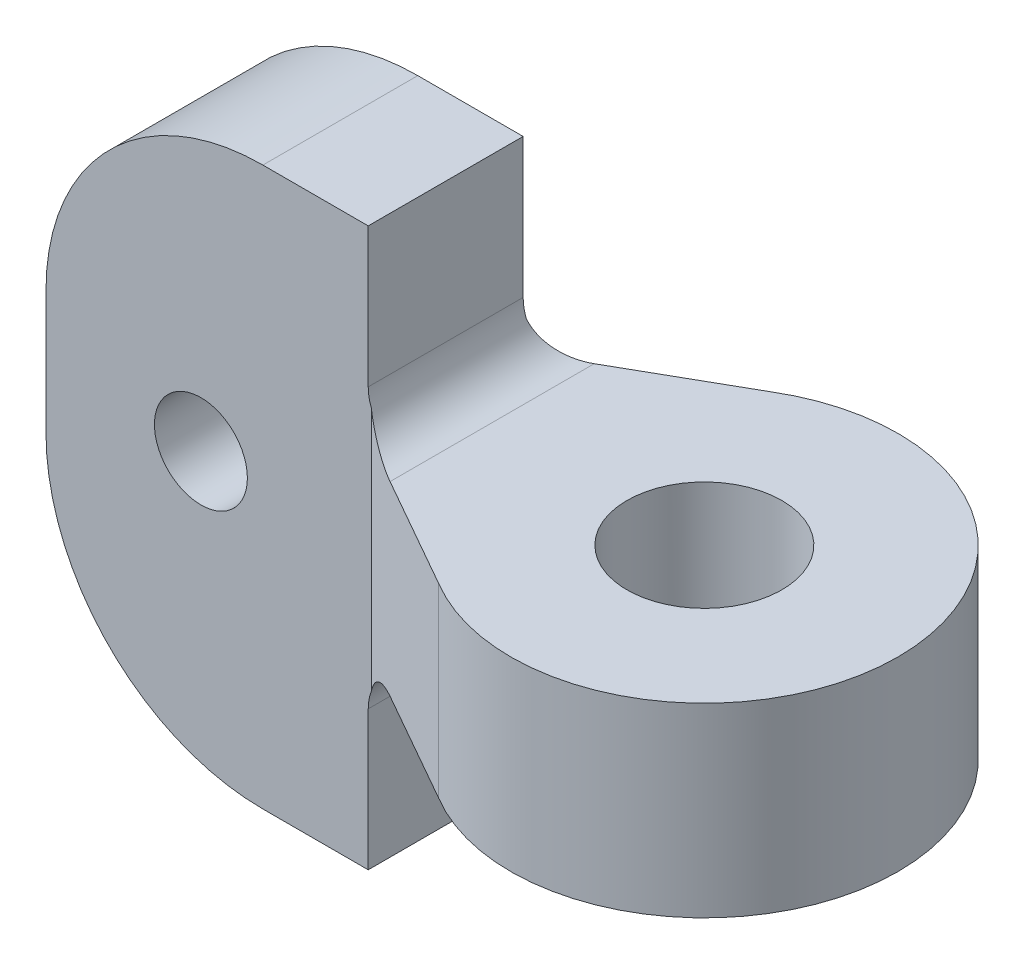
SolidWorks part; units mm, degrees
ref_plane "Alzado" through (0, 0, 0) normal (0, 0, 1) x (1, 0, 0)
ref_plane "Planta" through (0, 0, 0) normal (0, 1, 0) x (1, 0, 0)
ref_plane "Vista lateral" through (0, 0, 0) normal (1, 0, 0) x (0, 0, -1)
sketch "Croquis1" plane through (0, 0, 0) normal (0, 0, 1) x (1, 0, 0)
  line L0 (11.25, 17.1) -> (11.25, 11.1)
  line L1 (5.75, -0.9) -> (11.25, -0.9)
  line L2 (-1.25, 6.1) -> (-1.25, 10.1)
  line L3 (5.75, 17.1) -> (11.25, 17.1)
  line L4 (11.25, 11.1) -> (23.75, 11.1)
  line L5 (-1.25, -0.9) -> (1.25, 0.9) construction
  line L6 (-1.25, 17.1) -> (-1.0254, 14.0276) construction
  line L7 (23.75, 11.1) -> (23.75, 5.1)
  line L9 (23.75, 5.1) -> (11.25, 5.1)
  line L10 (11.25, 5.1) -> (11.25, -0.9)
  line L13 (11.25, 17.1) -> (-1.25, 17.1) construction
  circle A0 centre (3.75, 8.1) radius 1.5
  arc A1 (-1.25, 10.1) -> (5.75, 17.1) centre (5.75, 10.1) cw
  arc A2 (5.75, -0.9) -> (-1.25, 6.1) centre (5.75, 6.1) cw
  point P0 (0, 0)
  dimension "D6" = 3
  dimension "D4" = 7
  dimension "D5" = 7
  dimension "D1" = 25
  dimension "D2" = 18
  dimension "D3" = 12.5
  dimension "D7" = 5
  dimension "D8" = 9
  dimension "D9" = 6
  dimension "D10" = 6
extrude "Saliente-Extruir1" add sketch "Croquis1" along normal blind 15
sketch "Croquis2" plane through (0, 0, 0) normal (0, 1, 0) x (1, 0, 0)
  line L0 (23.75, -7.5) -> (11.25, -7.5) construction
  line L1 (23.75, -15) -> (23.75, 0) construction
  line L2 (11.25, -15) -> (11.25, 0) construction
  line L3 (17.5, -1.25) -> (11.25, 0)
  line L4 (17.5, -13.75) -> (11.25, -15)
  line L5 (11.25, -15) -> (11.25, -17.9613)
  line L6 (11.25, -17.9613) -> (29.6635, -17.9613)
  line L7 (29.6635, -17.9613) -> (29.6635, 1.8686)
  line L8 (29.6635, 1.8686) -> (11.1263, 1.8686)
  line L9 (11.1263, 1.8686) -> (11.25, 0)
  circle A0 centre (17.5, -7.5) radius 2.5
  arc A1 (17.5, -13.75) -> (17.5, -1.25) centre (17.5, -7.5) ccw
  dimension "D1" = 5
extrude "Cortar-Extruir1" cut sketch "Croquis2" along normal blind 20
sketch "Croquis3" plane through (0, 17.1, 0) normal (0, 1, 0) x (1, 0, 0)
  line L0 (-1.25, -7.5) -> (23.75, -7.5) construction
  line L1 (-1.25, -15) -> (-1.25, 0) construction
  line L2 (17.5, -1.25) -> (17.5, -13.75) construction
  line L3 (-4.1301, -10) -> (9.25, -10)
  line L4 (-13.75, -10) -> (-13.75, -5)
  line L5 (-3.4648, -5) -> (9.25, -5)
  line L6 (9.25, -5) -> (14.2844, -2.1407)
  line L7 (-1.25, -7.5) -> (11.25, -5) construction
  line L8 (-1.25, -7.5) -> (11.25, -10) construction
  line L11 (17.5, -1.25) -> (17.5, 1.6772)
  line L12 (17.5, 1.6772) -> (-3.4648, 1.6772)
  line L13 (-3.4648, 1.6772) -> (-3.4648, -5)
  line L14 (17.5, -13.75) -> (17.5, -15.5814)
  line L15 (17.5, -15.5814) -> (-4.1301, -15.5814)
  line L16 (-4.1301, -15.5814) -> (-4.1301, -10)
  line L17 (11.25, -15) -> (11.25, 0) construction
  line L18 (9.25, -10) -> (14.2844, -12.8593)
  arc A0 (17.5, -13.75) -> (17.5, -1.25) centre (17.5, -7.5) ccw construction
  arc A1 (17.5, -1.25) -> (14.2844, -2.1407) centre (17.5, -7.5) ccw
  arc A2 (14.2844, -12.8593) -> (17.5, -13.75) centre (17.5, -7.5) ccw
  dimension "D1" = 5
  dimension "D2" = 25
  dimension "D3" = 2
extrude "Cortar-Extruir2" cut sketch "Croquis3" against normal blind 22
ref_plane "Plano1" through (0, 0, 7.5) normal (0, 0, 1) x (1, 0, 0)
sketch "Croquis4" plane through (0, 0, 10) normal (0, 0, 1) x (1, 0, 0)
  line L0 (5.75, -0.9) -> (9.25, -0.9) construction
  line L1 (11.25, 17.1) -> (9.15, 17.1)
  line L2 (11.25, 17.1) -> (11.25, 11.1)
  line L3 (11.25, 11.1) -> (9.15, 11.1)
  line L4 (9.15, 17.1) -> (9.15, 11.1)
  line L5 (11.25, 5.1) -> (9.15, 5.1)
  line L6 (11.25, 5.1) -> (11.25, -0.9)
  line L7 (11.25, -0.9) -> (9.15, -0.9)
  line L8 (9.15, 5.1) -> (9.15, -0.9)
  dimension "D1" = 2.1
  dimension "D2" = 2.1
extrude "Cortar-Extruir4" cut sketch "Croquis4" against normal mid plane 20
fillet "Redondeo1" radius 1.5 2 edges at (9.15, 5.1, 7.5) (9.15, 11.1, 7.5)
